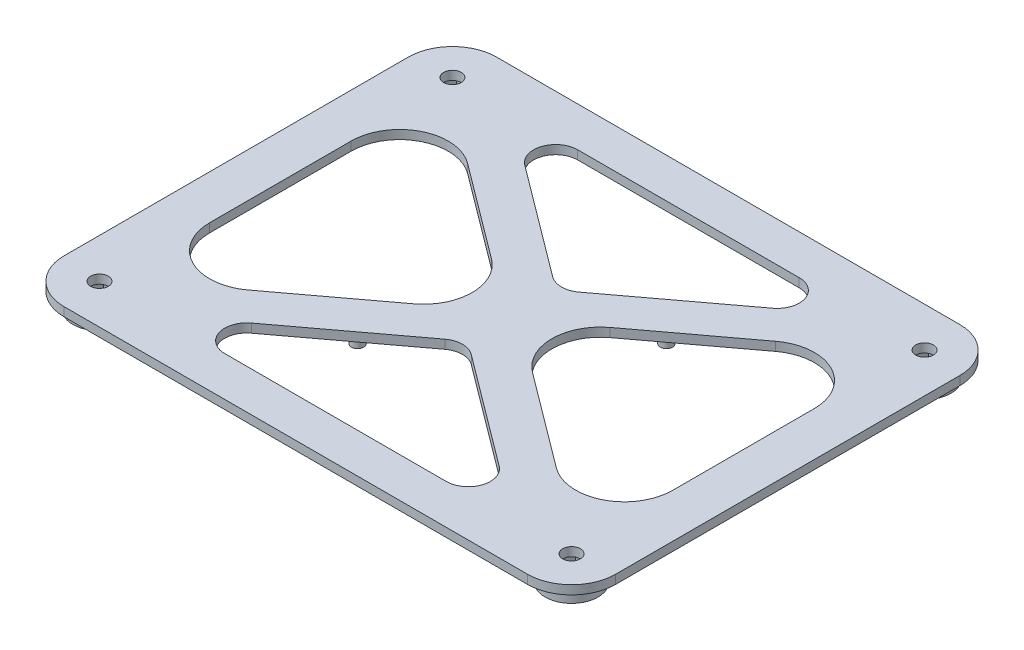
SolidWorks part; units mm, degrees
ref_plane "Front Plane" through (0, 0, 0) normal (0, 0, 1) x (1, 0, 0)
ref_plane "Top Plane" through (0, 0, 0) normal (0, 1, 0) x (1, 0, 0)
ref_plane "Right Plane" through (0, 0, 0) normal (1, 0, 0) x (0, 0, -1)
sketch "Sketch1" plane through (0, 0, 0) normal (0, 1, 0) x (1, 0, 0)
  line L0 (-53.5, 40) -> (-62.5, 40) construction
  line L24 (-52.5, -49) -> (52.5, -49)
  line L25 (-62.5, -39) -> (-62.5, 39)
  line L29 (-53.5, 40) -> (-53.5, 49) construction
  line L49 (-52.5, 49) -> (52.5, 49)
  line L50 (-49.032, 40.5356) -> (-51.7298, 44.1372)
  line L51 (-51.7298, 44.1372) -> (-56.1978, 43.6016)
  line L52 (-56.1978, 43.6016) -> (-57.968, 39.4644)
  line L53 (-57.968, 39.4644) -> (-55.2702, 35.8628)
  line L54 (-55.2702, 35.8628) -> (-50.8022, 36.3984)
  line L55 (-50.8022, 36.3984) -> (-49.032, 40.5356)
  line L56 (62.5, -39) -> (62.5, 39)
  line L57 (-62.5, -49) -> (62.5, 49) construction
  line L58 (-62.5, 49) -> (62.5, -49) construction
  line L59 (57.968, 40.5356) -> (55.2702, 44.1372)
  line L60 (55.2702, 44.1372) -> (50.8022, 43.6016)
  line L61 (50.8022, 43.6016) -> (49.032, 39.4644)
  line L62 (49.032, 39.4644) -> (51.7298, 35.8628)
  line L63 (51.7298, 35.8628) -> (56.1978, 36.3984)
  line L64 (56.1978, 36.3984) -> (57.968, 40.5356)
  line L65 (57.968, -39.4644) -> (55.2702, -35.8628)
  line L66 (55.2702, -35.8628) -> (50.8022, -36.3984)
  line L67 (50.8022, -36.3984) -> (49.032, -40.5356)
  line L68 (49.032, -40.5356) -> (51.7298, -44.1372)
  line L69 (51.7298, -44.1372) -> (56.1978, -43.6016)
  line L70 (56.1978, -43.6016) -> (57.968, -39.4644)
  line L71 (-49.032, -39.4644) -> (-51.7298, -35.8628)
  line L72 (-51.7298, -35.8628) -> (-56.1978, -36.3984)
  line L73 (-56.1978, -36.3984) -> (-57.968, -40.5356)
  line L74 (-57.968, -40.5356) -> (-55.2702, -44.1372)
  line L75 (-55.2702, -44.1372) -> (-50.8022, -43.6016)
  line L76 (-50.8022, -43.6016) -> (-49.032, -39.4644)
  circle A6 centre (53.5, 40) radius 6
  circle A8 centre (53.5, 40) radius 2
  circle A14 centre (-53.5, 40) radius 2
  circle A15 centre (-53.5, 40) radius 4.5 construction
  circle A16 centre (-53.5, 40) radius 6
  circle A17 centre (53.5, -40) radius 6
  circle A18 centre (53.5, -40) radius 2
  circle A19 centre (-53.5, -40) radius 6
  circle A20 centre (-53.5, -40) radius 2
  arc A21 (-52.5, -49) -> (-62.5, -39) centre (-52.5, -39) cw
  arc A22 (52.5, -49) -> (62.5, -39) centre (52.5, -39) ccw
  arc A23 (52.5, 49) -> (62.5, 39) centre (52.5, 39) cw
  arc A24 (-62.5, 39) -> (-52.5, 49) centre (-52.5, 39) cw
  point P0 (0, 0)
  point P5 (0, 0)
  point P49 (0, 0)
  dimension "D18" = 4
  dimension "D20" = 9
  dimension "D21" = 12
  dimension "D8" = 10
  dimension "D5" = 9
  dimension "D6" = 2
  dimension "D7" = 2
  dimension "D3" = 125
  dimension "D4" = 98
extrude "Boss-Extrude1" add sketch "Sketch1" along normal blind 2 contours A24 L25 A21 L24 A22 L56 A23 L49 A19 A17 A16 A6 | A6 L64 L63 L62 L61 L60 L59 | L63 L64 L59 L60 L61 L62 A8 | A17 L70 L69 L68 L67 L66 L65 | L69 L70 L65 L66 L67 L68 A18 | A19 L76 L75 L74 L73 L72 L71 | L75 L76 L71 L72 L73 L74 A20 | A16 L55 L54 L53 L52 L51 L50 | L54 L55 L50 L51 L52 L53 A14
extrude "Boss-Extrude2" add sketch "Sketch1<3>" against normal blind 3.5 contours A16 L55 L54 L53 L52 L51 L50 | A6 L64 L63 L62 L61 L60 L59 | A17 L70 L69 L68 L67 L66 L65 | A19 L76 L75 L74 L73 L72 L71
sketch "Sketch1<3>" plane through (0, 0, 0) normal (0, 1, 0) x (1, 0, 0) same geometry as "Sketch1"
sketch "Sketch2" plane through (0, 0, 0) normal (0, 1, 0) x (1, 0, 0)
  line L0 (0, 0) -> (-53.5, 40) construction
  line L1 (-53.5, 40) -> (-53.5, -40) construction
  line L2 (-53.5, -40) -> (0, 0) construction
  line L3 (-53.5, 40) -> (53.5, 40) construction
  line L4 (53.5, 40) -> (0, 0) construction
  line L5 (0, 0) -> (53.5, -40) construction
  line L6 (53.5, -40) -> (53.5, 40) construction
  line L7 (53.5, -40) -> (-53.5, -40) construction
  line L9 (13.4532, -8.8099) -> (34.9132, -24.8547)
  line L10 (52.5, -16.0448) -> (52.5, 16.0448)
  line L11 (34.9132, 24.8547) -> (13.4532, 8.8099)
  line L12 (-13.4532, 8.8099) -> (-34.9132, 24.8547)
  line L13 (-52.5, 16.0448) -> (-52.5, -16.0448)
  line L14 (-34.9132, -24.8547) -> (-13.4532, -8.8099)
  line L15 (-2.994, 12.2273) -> (-28.0965, 30.9955)
  line L17 (28.0965, 30.9955) -> (2.994, 12.2273)
  line L18 (2.994, -12.2273) -> (28.0965, -30.9955)
  line L20 (-28.0965, -30.9955) -> (-2.994, -12.2273)
  line L21 (29.44, 32) -> (0, 9.9888) construction
  line L22 (0, 9.9888) -> (-29.44, 32) construction
  line L23 (-29.44, -32) -> (0, -9.9888) construction
  line L24 (0, -9.9888) -> (29.44, -32) construction
  line L25 (29.44, -32) -> (-29.44, -32) construction
  line L26 (-29.44, 32) -> (29.44, 32) construction
  line L27 (25.1025, 40) -> (-25.1025, 40)
  line L28 (-25.1025, -40) -> (25.1025, -40)
  line L29 (-52.5, -38.0037) -> (-1.67, 0) construction
  line L30 (-52.5, 38.0037) -> (-52.5, -38.0037) construction
  line L31 (-1.67, 0) -> (-52.5, 38.0037) construction
  line L32 (52.5, -38.0037) -> (52.5, 38.0037) construction
  line L33 (52.5, 38.0037) -> (1.67, 0) construction
  line L34 (1.67, 0) -> (52.5, -38.0037) construction
  circle A12 centre (17.5, 17.5) radius 1.4
  circle A13 centre (17.5, -17.5) radius 1.4
  circle A14 centre (-17.5, -17.5) radius 1.4
  circle A15 centre (-17.5, 17.5) radius 1.4
  arc A16 (-34.9132, -24.8547) -> (-52.5, -16.0448) centre (-41.5, -16.0448) cw
  arc A17 (-13.4532, -8.8099) -> (-13.4532, 8.8099) centre (-20.04, 0) ccw
  arc A18 (-34.9132, 24.8547) -> (-52.5, 16.0448) centre (-41.5, 16.0448) ccw
  arc A19 (52.5, 16.0448) -> (34.9132, 24.8547) centre (41.5, 16.0448) ccw
  arc A20 (52.5, -16.0448) -> (34.9132, -24.8547) centre (41.5, -16.0448) cw
  arc A21 (13.4532, 8.8099) -> (13.4532, -8.8099) centre (20.04, 0) ccw
  arc A22 (-2.994, -12.2273) -> (2.994, -12.2273) centre (0, -16.2318) cw
  arc A23 (28.0965, -30.9955) -> (25.1025, -40) centre (25.1025, -35) cw
  arc A24 (-25.1025, -40) -> (-28.0965, -30.9955) centre (-25.1025, -35) cw
  arc A25 (28.0965, 30.9955) -> (25.1025, 40) centre (25.1025, 35) ccw
  arc A26 (-2.994, 12.2273) -> (2.994, 12.2273) centre (0, 16.2318) ccw
  arc A27 (-28.0965, 30.9955) -> (-25.1025, 40) centre (-25.1025, 35) cw
  point P44 (40.14, -40)
  point P47 (-40.14, -40)
  point P50 (40.14, 40)
  point P56 (-40.14, 40)
  dimension "D3" = 11
  dimension "D4" = 5
  dimension "D5" = 2.8
  dimension "D6" = 17.5
  dimension "D7" = 17.5
  dimension "D1" = 1
  dimension "D2" = 8
  dimension "D8" = 4
extrude "Cut-Extrude2" cut sketch "Sketch2<4>" along normal blind 10 contours A21 L11 A19 L10 A20 L9 | L15 A27 L27 A25 L17 A26 | A18 L12 A17 L14 A16 L13 | L28 A24 L20 A22 L18 A23 region at (34.7811, 0, 0) region at (-34.7811, 0, 0) region at (0, 0, -29.4441) region at (0, 0, 29.4441)
sketch "Sketch2<4>" plane through (0, 0, 0) normal (0, 1, 0) x (1, 0, 0) same geometry as "Sketch2"
extrude "Boss-Extrude4" add sketch "Sketch2" against normal blind 3.5 contours A12 | A14 | A13 | A15 | A14 region at (17.5, 0, -17.5) region at (17.5, 0, 17.5) region at (-17.5, 0, 17.5)
fillet "Fillet3" radius 1 4 edges at (17.5, 0, -18.9) (17.5, 0, 16.1) (-17.5, 0, 16.1) (-17.5, 0, -16.1)
